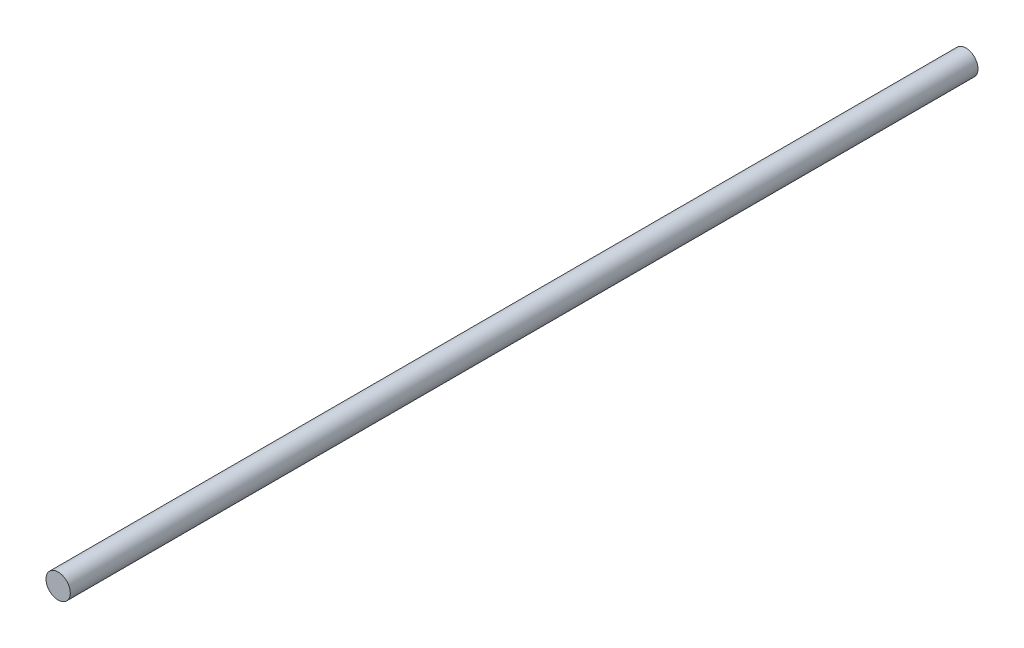
SolidWorks part; units mm, degrees
ref_plane "Front Plane" through (0, 0, 0) normal (0, 0, 1) x (1, 0, 0)
ref_plane "Top Plane" through (0, 0, 0) normal (0, 1, 0) x (1, 0, 0)
ref_plane "Right Plane" through (0, 0, 0) normal (1, 0, 0) x (0, 0, -1)
sketch "Sketch1" plane through (0, 0, 0) normal (0, 0, 1) x (1, 0, 0)
  circle A0 centre (0, 0) radius 2.3813
  dimension "D1" = 4.7625
extrude "Boss-Extrude1" add sketch "Sketch1" along normal mid plane 177.8
